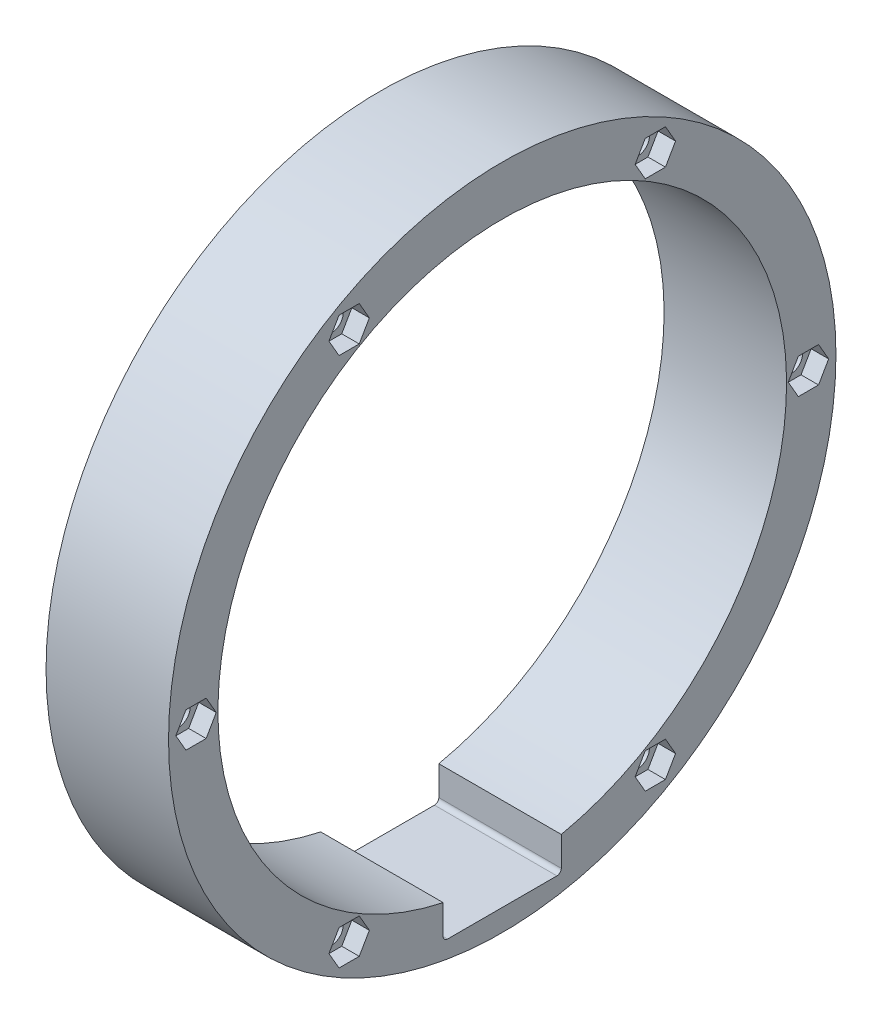
SolidWorks part; units mm, degrees
ref_plane "Front Plane" through (0, 0, 0) normal (0, 0, 1) x (1, 0, 0)
ref_plane "Top Plane" through (0, 0, 0) normal (0, 1, 0) x (1, 0, 0)
ref_plane "Right Plane" through (0, 0, 0) normal (1, 0, 0) x (0, 0, -1)
sketch "Sketch1" plane through (0, 0, 0) normal (1, 0, 0) x (0, 0, -1)
  circle A0 centre (0, 0) radius 76.29
  circle A1 centre (0, 0) radius 65
  dimension "D1" = 152.58
  dimension "D2" = 130
extrude "Boss-Extrude1" add sketch "Sketch1" along normal blind 28
sketch "Sketch2" plane through (28, 0, 0) normal (1, 0, 0) x (0, 0, -1)
  line L0 (0, -34.8517) -> (0, -97.703) construction
  line L1 (-13.5, -51.894) -> (13.5, -51.894)
  line L2 (-13.5, -51.894) -> (-13.5, -70.29)
  line L3 (-12.5, -71.29) -> (12.5, -71.29)
  line L4 (13.5, -51.894) -> (13.5, -70.29)
  circle A1 centre (0, 0) radius 76.29 construction
  arc A2 (-13.5, -70.29) -> (-12.5, -71.29) centre (-12.5, -70.29) ccw
  arc A3 (13.5, -70.29) -> (12.5, -71.29) centre (12.5, -70.29) cw
  point P6 (0, -51.894)
  point P10 (0, -76.29)
  dimension "D2" = 1
  dimension "D3" = 1
  dimension "D1" = 5
  dimension "D4" = 27
extrude "Cut-Extrude1" cut sketch "Sketch2" against normal up to next
sketch "Sketch3" plane through (28, 0, 0) normal (1, 0, 0) x (0, 0, -1)
  line L0 (-94.7404, 0) -> (95.285, 0) construction
  circle A0 centre (-70, 0) radius 2.65
  circle A1 centre (-35, 60.6218) radius 2.65
  circle A2 centre (35, 60.6218) radius 2.65
  circle A3 centre (70, 0) radius 2.65
  circle A4 centre (35, -60.6218) radius 2.65
  circle A5 centre (-35, -60.6218) radius 2.65
  point P17 (0, 0)
  dimension "D1" = 5.3
  dimension "D2" = 70
  dimension "D3" = 6
extrude "Cut-Extrude2" cut sketch "Sketch3" against normal up to next
sketch "Sketch4" plane through (28, 0, 0) normal (1, 0, 0) x (0, 0, -1)
  line L0 (-37.3094, 56.6218) -> (-32.6906, 56.6218)
  line L1 (-67.6906, -4) -> (-65.3812, 0)
  line L2 (-65.3812, 0) -> (-67.6906, 4)
  line L3 (-67.6906, 4) -> (-72.3094, 4)
  line L4 (-72.3094, 4) -> (-74.6188, 0)
  line L5 (-74.6188, 0) -> (-72.3094, -4)
  line L6 (-72.3094, -4) -> (-67.6906, -4)
  line L7 (-32.6906, 56.6218) -> (-30.3812, 60.6218)
  line L8 (-30.3812, 60.6218) -> (-32.6906, 64.6218)
  line L9 (-32.6906, 64.6218) -> (-37.3094, 64.6218)
  line L10 (-37.3094, 64.6218) -> (-39.6188, 60.6218)
  line L11 (-39.6188, 60.6218) -> (-37.3094, 56.6218)
  line L12 (30.3812, 60.6218) -> (32.6906, 56.6218)
  line L13 (32.6906, 56.6218) -> (37.3094, 56.6218)
  line L14 (37.3094, 56.6218) -> (39.6188, 60.6218)
  line L15 (39.6188, 60.6218) -> (37.3094, 64.6218)
  line L16 (37.3094, 64.6218) -> (32.6906, 64.6218)
  line L17 (32.6906, 64.6218) -> (30.3812, 60.6218)
  line L18 (67.6906, 4) -> (65.3812, 0)
  line L19 (65.3812, 0) -> (67.6906, -4)
  line L20 (67.6906, -4) -> (72.3094, -4)
  line L21 (72.3094, -4) -> (74.6188, 0)
  line L22 (74.6188, 0) -> (72.3094, 4)
  line L23 (72.3094, 4) -> (67.6906, 4)
  line L24 (37.3094, -56.6218) -> (32.6906, -56.6218)
  line L25 (32.6906, -56.6218) -> (30.3812, -60.6218)
  line L26 (30.3812, -60.6218) -> (32.6906, -64.6218)
  line L27 (32.6906, -64.6218) -> (37.3094, -64.6218)
  line L28 (37.3094, -64.6218) -> (39.6188, -60.6218)
  line L29 (39.6188, -60.6218) -> (37.3094, -56.6218)
  line L30 (-30.3812, -60.6218) -> (-32.6906, -56.6218)
  line L31 (-32.6906, -56.6218) -> (-37.3094, -56.6218)
  line L32 (-37.3094, -56.6218) -> (-39.6188, -60.6218)
  line L33 (-39.6188, -60.6218) -> (-37.3094, -64.6218)
  line L34 (-37.3094, -64.6218) -> (-32.6906, -64.6218)
  line L35 (-32.6906, -64.6218) -> (-30.3812, -60.6218)
  circle A0 centre (-70, 0) radius 4 construction
  circle A1 centre (-35, 60.6218) radius 4 construction
  circle A2 centre (35, 60.6218) radius 4 construction
  circle A3 centre (70, 0) radius 4 construction
  circle A4 centre (35, -60.6218) radius 4 construction
  circle A5 centre (-35, -60.6218) radius 4 construction
  point P52 (0, 0)
  dimension "D1" = 8
  dimension "D2" = 6
extrude "Cut-Extrude3" cut sketch "Sketch4" against normal blind 4
